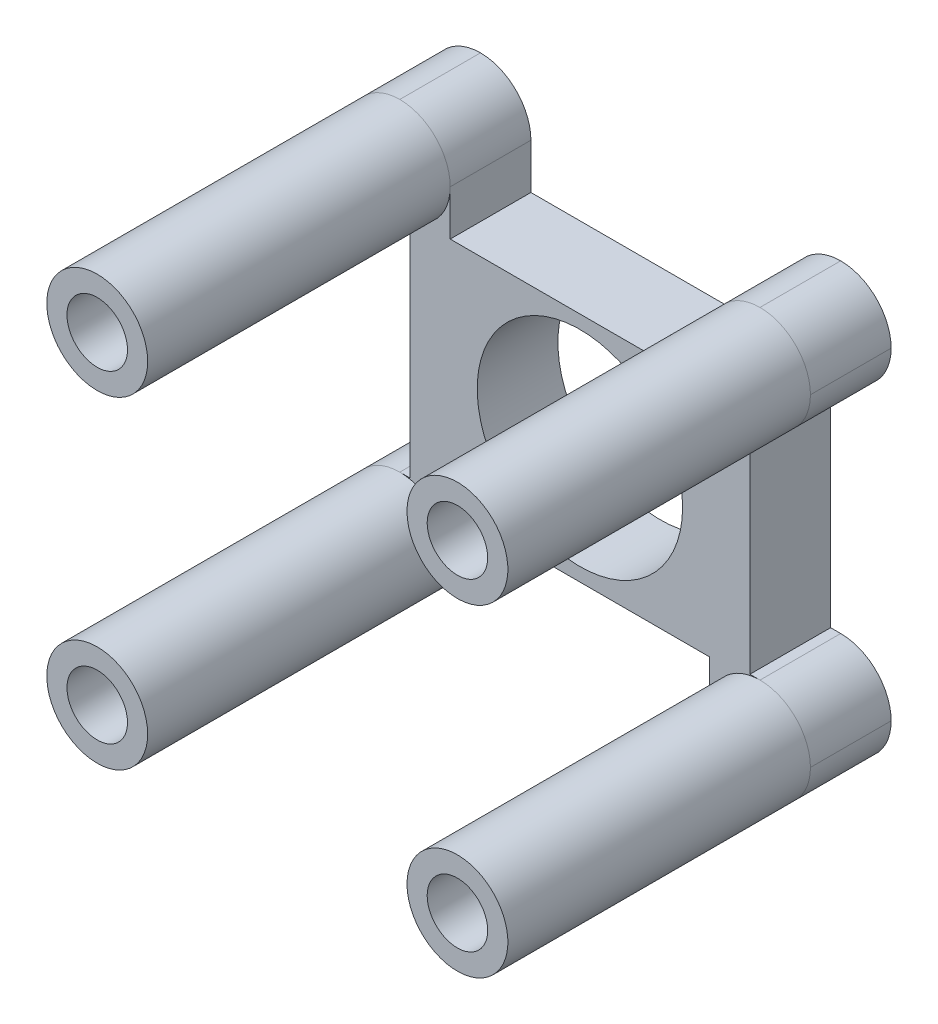
SolidWorks part; units mm, degrees
ref_plane "Front Plane" through (0, 0, 0) normal (0, 0, 1) x (1, 0, 0)
ref_plane "Top Plane" through (0, 0, 0) normal (0, 1, 0) x (1, 0, 0)
ref_plane "Right Plane" through (0, 0, 0) normal (1, 0, 0) x (0, 0, -1)
sketch "Sketch1" plane through (0, 0, 0) normal (0, 0, 1) x (1, 0, 0)
  line L9 (0, 7.4941) -> (0, -7.4941)
  line L27 (-4.5637, -6.6509) -> (-4.5637, -5.75)
  line L34 (6.4286, -10.5) -> (11.4286, -10.5)
  line L35 (-6.4286, 5.7554) -> (6.4286, 5.7554)
  line L36 (-6.4286, 5.7554) -> (-6.4286, -5.7554)
  line L37 (-6.4286, -5.7554) -> (6.4286, -5.7554)
  line L38 (6.4286, 5.7554) -> (6.4286, -5.7554)
  line L39 (-6.4286, 5.7554) -> (6.4286, -5.7554) construction
  line L40 (-6.4286, -5.7554) -> (6.4286, 5.7554) construction
  line L41 (-6.4286, 10.5) -> (-11.4286, 10.5)
  line L42 (-6.4286, 10.5) -> (-6.4286, -10.5)
  line L43 (-6.4286, -10.5) -> (-11.4286, -10.5)
  line L44 (-11.4286, 10.5) -> (-11.4286, -10.5)
  line L45 (11.4286, 10.5) -> (11.4286, -10.5)
  line L46 (6.4286, 10.5) -> (6.4286, -10.5)
  line L47 (6.4286, 10.5) -> (11.4286, 10.5)
  circle A0 centre (0, 0) radius 5.0909
  circle A2 centre (0, 0) radius 16
  point P0 (0, 0)
  point P3 (0, 0)
  point P9 (0, 0)
  point P12 (-11.4286, 0)
extrude "Boss-Extrude3" add sketch "Sketch1" along normal blind 4 contours A0 L9 L37 L38 L35 | A0 L9 L35 L36 L37 | L41 L44 L43 L42 L36 | L47 L46 L38 L34 L45 region at (3.2143, 5.6235, 0) region at (-0.1318, 5.4231, 0) region at (-8.9286, 0, 0) region at (8.9286, 0, 0)
sketch "Sketch2" plane through (0, 0, 4) normal (0, 0, 1) x (1, 0, 0)
  line L1 (-11.4286, 10.5) -> (-11.4286, -10.5) construction
  line L2 (-6.4286, 10.5) -> (-11.4286, 10.5) construction
  circle A0 centre (-8.9286, 8) radius 1.5
  circle A1 centre (-8.9286, 8) radius 2.5
  dimension "D1" = 2.5
  dimension "D2" = 2.5
extrude "Boss-Extrude4" add sketch "Sketch2" along normal blind 15
mirror "Mirror1" about plane through (0, 0, 0) normal (1, 0, 0) of "Boss-Extrude4"
mirror "Mirror2" about plane through (0, 0, 0) normal (0, 1, 0) of "Mirror1"
fillet "Fillet1" radius 2.5 8 edges at (-11.4286, 10.5, 2) (-11.4286, -10.5, 2) (-6.4286, -10.5, 2) (6.4286, -10.5, 2) (11.4286, -10.5, 2) (11.4286, 10.5, 2) (6.4286, 10.5, 2) (-6.4286, 10.5, 2)
sketch "Sketch3" plane through (0, 0, 4) normal (0, 0, 1) x (1, 0, 0)
  line L1 (-11.4286, 5.5) -> (-8.4286, 5.5)
  line L2 (-11.4286, 5.5) -> (-11.4286, -5.5)
  line L3 (-11.4286, -5.5) -> (-8.4286, -5.5)
  line L4 (-8.4286, 5.5) -> (-8.4286, -5.5)
  line L7 (-11.4286, 8) -> (-11.4286, -8) construction
  point P7 (-8.4286, 0)
extrude "Cut-Extrude1" cut sketch "Sketch3" against normal up to next
fillet "Fillet2" radius 2.5 1 edges at (-11.4286, 5.5, 2)
mirror "Mirror3" about plane through (0, 0, 0) normal (1, 0, 0) of "Cut-Extrude1"
fillet "Fillet3" radius 2.5 3 edges at (-11.4286, -5.5, 2) (11.4286, -5.5, 2) (11.4286, 5.5, 2)
